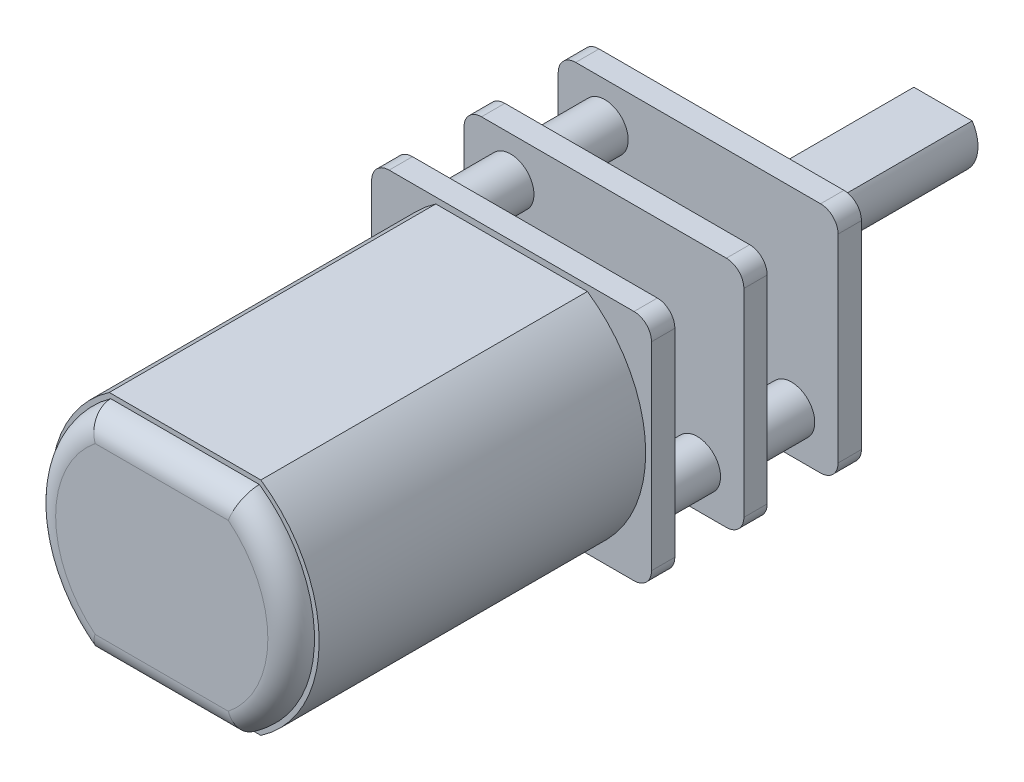
SolidWorks part; units mm, degrees
ref_plane "Front Plane" through (0, 0, 0) normal (0, 0, 1) x (1, 0, 0)
ref_plane "Top Plane" through (0, 0, 0) normal (0, 1, 0) x (1, 0, 0)
ref_plane "Right Plane" through (0, 0, 0) normal (1, 0, 0) x (0, 0, -1)
sketch "Sketch1" plane through (0, 0, 0) normal (0, 0, 1) x (1, 0, 0)
  line L0 (-3.25, 4.7434) -> (3.25, 4.7434)
  line L1 (5.75, 0) -> (-5.75, 0) construction
  line L2 (-3.25, -4.7434) -> (3.25, -4.7434)
  circle A0 centre (0, 0) radius 5.75
  dimension "D1" = 11.5
  dimension "D2" = 6.5
extrude "Boss-Extrude1" add sketch "Sketch1" along normal blind 14 contours L1 A0 L0 | A0 L1 L2 region at (0, 2.1869, 0) region at (0, -2.1869, 0)
sketch "Sketch2" plane through (0, 0, 0) normal (0, 0, 1) x (1, 0, 0)
  line L0 (-3.25, 4.7434) -> (3.25, 4.7434) construction
  line L2 (-3.25, -4.7434) -> (3.25, -4.7434) construction
  circle A0 centre (4, -3.2434) radius 1
  circle A3 centre (-4, 3.2434) radius 1
  dimension "D2" = 2
  dimension "D5" = 2
  dimension "D1" = 4
  dimension "D3" = 1.5
  dimension "D4" = 1.5
  dimension "D6" = 4
extrude "Boss-Extrude2" add sketch "Sketch2" against normal blind 9
sketch "Sketch3" plane through (0, 0, 0) normal (1, 0, 0) x (0, 0, -1)
  line L1 (0, 5) -> (1, 5)
  line L2 (0, 5) -> (0, -5)
  line L3 (0, -5) -> (1, -5)
  line L4 (1, 5) -> (1, -5)
  line L5 (3.9597, 5) -> (4.9597, 5)
  line L6 (3.9597, 5) -> (3.9597, -5)
  line L7 (3.9597, -5) -> (4.9597, -5)
  line L8 (4.9597, 5) -> (4.9597, -5)
  line L9 (9, 5) -> (8, 5)
  line L10 (9, 5) -> (9, -5)
  line L11 (9, -5) -> (8, -5)
  line L12 (8, 5) -> (8, -5)
  line L15 (9, 2.2434) -> (9, 4.2434) construction
  dimension "D1" = 5
  dimension "D2" = 1
  dimension "D3" = 1
  dimension "D4" = 1
  dimension "D5" = 5
extrude "Boss-Extrude3" add sketch "Sketch3" along normal blind 6 and the other way blind 6
sketch "Sketch4" plane through (0, 0, -9) normal (0, 0, -1) x (-1, 0, 0)
  circle A0 centre (0, 0) radius 2
  circle A1 centre (0, 0) radius 1.5
  dimension "D1" = 4
  dimension "D2" = 0.5
extrude "Boss-Extrude4" add sketch "Sketch4" along normal blind 0.75
sketch "Sketch5" plane through (0, 0, -9) normal (0, 0, -1) x (-1, 0, 0)
  circle A0 centre (0, 0) radius 1.5
extrude "Boss-Extrude5" add sketch "Sketch5" along normal blind 3.5
sketch "Sketch6" plane through (0, 0, -12.5) normal (0, 0, -1) x (-1, 0, 0)
  line L0 (-1.25, 0.8292) -> (1.25, 0.8292)
  circle A0 centre (0, 0) radius 1.5
  circle A1 centre (0, 0) radius 1.5 construction
  circle M2 centre (0, 0) radius 1.5
  dimension "D2" = 0
  dimension "D1" = 2.5
extrude "Boss-Extrude6" add sketch "Sketch6" along normal blind 6 contours L0 M2 region at (0, -0.2211, -12.5)
sketch "Sketch7" plane through (0, 0, 14) normal (0, 0, 1) x (1, 0, 0)
  line L4 (-3.1875, -4.5434) -> (3.1875, -4.5434)
  line L5 (3.1875, 4.5434) -> (-3.1875, 4.5434)
  line L6 (-3.1875, -4.5434) -> (3.1875, -4.5434)
  line L7 (3.1875, 4.5434) -> (-3.1875, 4.5434)
  arc A4 (-3.1875, 4.5434) -> (-3.1875, -4.5434) centre (0, 0) ccw
  arc A5 (3.1875, -4.5434) -> (3.1875, 4.5434) centre (0, 0) ccw
  arc A6 (-3.1875, 4.5434) -> (-3.1875, -4.5434) centre (0, 0) ccw
  arc A7 (3.1875, -4.5434) -> (3.1875, 4.5434) centre (0, 0) ccw
  dimension "D1" = 0.2
extrude "Boss-Extrude7" add sketch "Sketch7" along normal blind 1
fillet "Fillet1" radius 1 4 edges at (0, 4.5434, 15) (5.55, 0, 15) (0, -4.5434, 15) (-5.55, 0, 15)
fillet "Fillet2" radius 0.75 12 edges at (-6, -5, -0.5) (-6, 5, -8.5) (-6, 5, -4.4597) (-6, 5, -0.5) (-6, -5, -4.4597) (-6, -5, -8.5) (6, -5, -0.5) (6, -5, -4.4597) (6, -5, -8.5) (6, 5, -8.5) (6, 5, -4.4597) (6, 5, -0.5)
